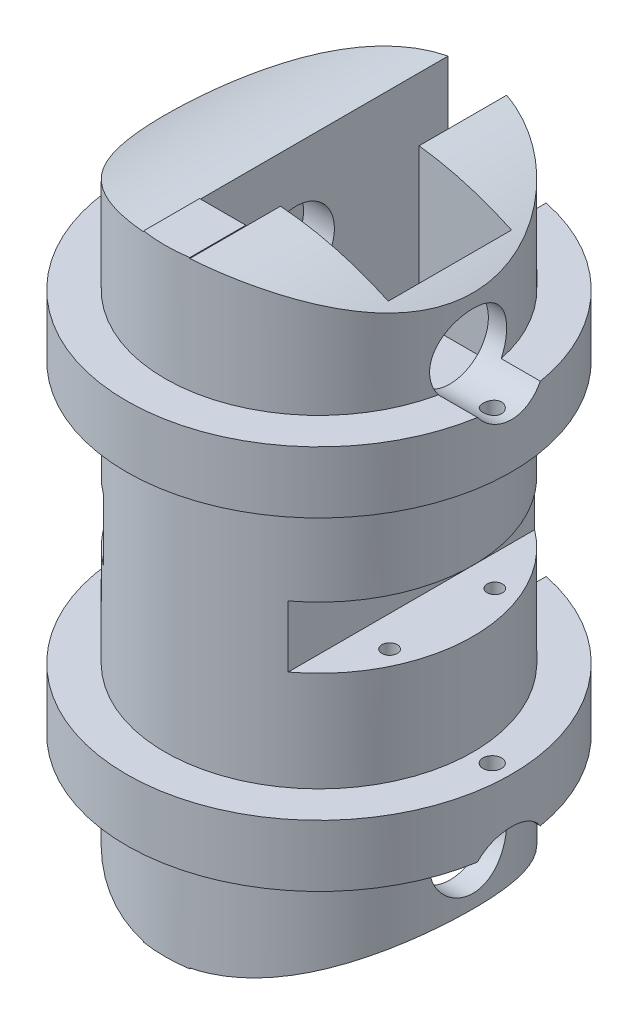
SolidWorks part; units mm, degrees
material "PET"
ref_plane "Front Plane" through (0, 0, 0) normal (0, 0, 1) x (1, 0, 0)
ref_plane "Top Plane" through (0, 0, 0) normal (0, 1, 0) x (1, 0, 0)
ref_plane "Right Plane" through (0, 0, 0) normal (1, 0, 0) x (0, 0, -1)
sketch "Sketch1" plane through (0, 0, 0) normal (0, 1, 0) x (1, 0, 0)
  circle A0 centre (0, 0) radius 10
  dimension "D1" = 20
extrude "Boss-Extrude1" add sketch "Sketch1" along normal mid plane 40
sketch "Sketch2" plane through (0, 0, 0) normal (0, 0, 1) x (1, 0, 0)
  circle A0 centre (0, 0) radius 20
  circle A1 centre (0, 0) radius 24.8561
extrude "Cut-Extrude3" cut sketch "Sketch2" against normal mid plane 40
ref_plane "Plane1" through (0, 20, 0) normal (0, 1, 0) x (1, 0, 0)
sketch "Sketch5" plane through (0, 20, 0) normal (0, 1, 0) x (1, 0, 0)
  line L1 (-1.5, 10) -> (1.5, 10)
  line L2 (-1.5, 10) -> (-1.5, -10)
  line L3 (-1.5, -10) -> (1.5, -10)
  line L4 (1.5, 10) -> (1.5, -10)
  point P4 (0, 10)
  point P6 (1.5, 0)
  dimension "D1" = 20
  dimension "D2" = 3
extrude "Cut-Extrude4" cut sketch "Sketch5" against normal blind 10
sketch "Sketch6" plane through (1.5, 0, 0) normal (-1, 0, 0) x (0, 0, 1)
  line L1 (9.8869, 19.9437) -> (-9.8869, 19.9437) construction
  circle A0 centre (0, 13.9437) radius 2.5
  circle A2 centre (0, 13.9437) radius 6
  dimension "D1" = 5
  dimension "D2" = 12
extrude "Cut-Extrude5" cut sketch "Sketch6" against normal blind 20 and the other way blind 5 contours A0
sketch "Sketch7" plane through (0, 20, 0) normal (0, 1, 0) x (1, 0, 0)
  line L0 (1.5, -9.8869) -> (1.5, 9.8869) construction
  line L1 (1.5, -4) -> (8.5, -4)
  line L2 (1.5, -4) -> (1.5, 4)
  line L3 (1.5, 4) -> (8.5, 4)
  line L4 (8.5, -4) -> (8.5, 4)
  point P4 (8.5, 0)
  point P8 (1.5, 0)
  dimension "D1" = 7
  dimension "D2" = 8
extrude "Cut-Extrude7" cut sketch "Sketch7" against normal up to surface (10 mm away) contours L1 L4 L3 L2 up to face at (0, 10, 0)
sketch "Sketch8" plane through (0, 10, 0) normal (0, 1, 0) x (1, 0, 0)
  line L0 (8.5, -4) -> (1.5, -4) construction
  line L1 (8.5, -4) -> (8.5, 4) construction
  circle A0 centre (8, -3.4149) radius 0.5
  dimension "D3" = 1
  dimension "D1" = 0.5851
  dimension "D2" = 0.5
extrude "Cut-Extrude8" cut sketch "Sketch8" against normal blind 30
sketch "Sketch9" plane through (0, 10, 0) normal (0, 1, 0) x (1, 0, 0)
  line L1 (0.5, 4) -> (2.5, 4)
  line L2 (0.5, 4) -> (0.5, 11.4751)
  line L3 (0.5, 11.4751) -> (2.5, 11.4751)
  line L4 (2.5, 4) -> (2.5, 11.4751)
  point P4 (1.5, 4)
  dimension "D1" = 2
extrude "Cut-Extrude9" cut sketch "Sketch9" along normal blind 23
mirror "Mirror2" about plane through (0, 0, 0) normal (0, 1, 0) of "Cut-Extrude9", "Cut-Extrude3", "Cut-Extrude5", "Cut-Extrude7", "Cut-Extrude8", "Cut-Extrude4"
mirror "Mirror3" about plane through (0, 0, 0) normal (0, 0, 1) of "Cut-Extrude8"
sketch "Sketch10" plane through (0, 10, 0) normal (0, 1, 0) x (1, 0, 0)
  line L0 (-1.5, 9.8869) -> (-1.5, -9.8869) construction
  line L1 (-1.5, -12.0623) -> (1.5, -12.0623)
  line L2 (-1.5, -12.0623) -> (-1.5, 12.1446)
  line L3 (-1.5, 12.1446) -> (1.5, 12.1446)
  line L4 (1.5, -12.0623) -> (1.5, 12.1446)
extrude "Cut-Extrude10" cut sketch "Sketch10" against normal blind 2.5
mirror "Mirror4" about plane through (0, 0, 0) normal (0, 1, 0) of "Cut-Extrude10"
sketch "Sketch11" plane through (0, -10, 0) normal (0, -1, 0) x (-1, 0, 0)
  line L1 (-0.5, -1.6113) -> (-2.5, -1.6113)
  line L2 (-0.5, -1.6113) -> (-0.5, -11.5424)
  line L3 (-0.5, -11.5424) -> (-2.5, -11.5424)
  line L4 (-2.5, -1.6113) -> (-2.5, -11.5424)
  line L5 (-1.5, -9.8869) -> (-1.5, 9.8869) construction
  point P4 (-1.5, -1.6113)
  dimension "D1" = 2
extrude "Cut-Extrude11" [suppressed] cut sketch "Sketch11" along normal blind 11.5
sketch "Sketch12" plane through (0, 0, 0) normal (0, 0, 1) x (1, 0, 0)
  line L0 (-10, 17.3205) -> (-10, -17.3205) construction
  line L1 (-10, -2) -> (10, -2)
  line L2 (-10, -2) -> (-10, 2)
  line L3 (-10, 2) -> (10, 2)
  line L4 (10, -2) -> (10, 2)
  line L5 (10, -11.4437) -> (10, 11.4437) construction
  line L7 (-6, 2) -> (6, 2)
  line L8 (-6, 2) -> (-6, -2)
  line L9 (-6, -2) -> (6, -2)
  line L10 (6, 2) -> (6, -2)
  point P8 (10, 0)
  dimension "D1" = 4
  dimension "D2" = 12
  dimension "D3" = 6
extrude "Cut-Extrude12" cut sketch "Sketch12" against normal mid plane 30 contours L8 L3 L2 L1 | L3 L10 L1 L4 region at (-8, 0, 0) region at (8, 0, 0)
sketch "Sketch13" plane through (0, 0, 0) normal (0, 0, 1) x (1, 0, 0)
  line L1 (-12, 6) -> (12, 6)
  line L2 (-12, 6) -> (-12, 10)
  line L3 (-12, 10) -> (12, 10)
  line L4 (12, 6) -> (12, 10)
  line L5 (-12, 10) -> (-7.9801, 10)
  line L6 (-12, 10) -> (-12, 6)
  line L7 (-12, 6) -> (-7.9801, 6)
  line L8 (-7.9801, 10) -> (-7.9801, 6)
  line L9 (12, 10) -> (8.9565, 10)
  line L10 (12, 10) -> (12, 6)
  line L11 (12, 6) -> (8.9565, 6)
  line L12 (8.9565, 10) -> (8.9565, 6)
  circle A0 centre (-10, 8) radius 1
  circle A1 centre (10, 8) radius 1
  point P4 (0, 6)
  point P11 (-12, 8)
  dimension "D6" = 2
  dimension "2" = 2
  dimension "D1" = 24
  dimension "D2" = 4
  dimension "D3" = 6
  dimension "D4" = 20
  dimension "D5" = 10
extrude "Boss-Extrude4" [suppressed] add sketch "Sketch13" along normal mid plane 2.5 contours L3 L12 L1 L4 A1 | L8 L3 L2 L1 A0
sketch "Sketch14" [suppressed] plane through (0, 0, 0) normal (0, 0, 1) x (1, 0, 0)
  line L0 (-10, 9) -> (-10, 7) construction
  circle A0 centre (10, 8) radius 1
  circle A1 centre (-10, 8) radius 1
ref_plane "Plane2" [suppressed] through (0, 8, 0) normal (0, 1, 0) x (1, 0, 0)
sketch "Sketch15" [suppressed] plane through (0, 8, 0) normal (0, 1, 0) x (1, 0, 0)
  arc A0 (-10, 0) -> (10, 0) centre (0, 0) ccw
sweep "Cut-Sweep1" [suppressed] cut path "Sketch15" circular profile diameter 2 parameters "D3"=2
sketch "Sketch29" [suppressed] plane through (0, 0, 0) normal (0, 0, 1) x (1, 0, 0)
  circle A0 centre (10, 8) radius 1
  circle A1 centre (-10, 8) radius 1
extrude "Cut-Extrude13" [suppressed] cut sketch "Sketch29" against normal blind 5
ref_plane "Plane3" [suppressed] through (0, 0, 0) normal (0, 0, 1) x (1, 0, 0)
sketch "Sketch36" [suppressed] plane through (0, 0, 0) normal (0, 0, 1) x (1, 0, 0)
  line L0 (10, 7) -> (10, 9) construction
  circle A0 centre (-10, 8) radius 1
  circle A1 centre (10, 8) radius 1
extrude "Cut-Extrude14" [suppressed] cut sketch "Sketch36" against normal up to surface and the other way up to surface
ref_plane "Plane4" through (0, 12.5, 0) normal (0, 1, 0) x (1, 0, 0)
sketch "Sketch37" plane through (0, 12.5, 0) normal (0, 1, 0) x (1, 0, 0)
  line L1 (-2.5, 16.1752) -> (2.5, 16.1752)
  line L2 (-2.5, 16.1752) -> (-2.5, 6.4344)
  line L3 (-2.5, 6.4344) -> (2.5, 6.4344)
  line L4 (2.5, 16.1752) -> (2.5, 6.4344)
  circle A0 centre (0, 0) radius 10
  circle A1 centre (0, 0) radius 12.5
  point P9 (0, 6.4344)
  dimension "D1" = 5
extrude "Boss-Extrude7" add sketch "Sketch37" against normal blind 4 contours L2 A1 L4 A0 region at (-2.8518, 12.5, -10.965)
mirror "Mirror5" about plane through (0, 0, 0) normal (0, 1, 0) of "Boss-Extrude7"
sketch "Sketch39" plane through (0, 0, 0) normal (1, 0, 0) x (0, 0, -1)
  circle A0 centre (0, 13.9437) radius 2.5
  circle A1 centre (0, -13.9437) radius 2.5
extrude "Cut-Extrude15" cut sketch "Sketch39" along normal blind 12.5
sketch "Sketch41" plane through (0, 7.5, 0) normal (0, 1, 0) x (1, 0, 0)
  line L0 (-1.5, -6.25) -> (1.5, -6.25)
  line L1 (-1.5, 9.8869) -> (-1.5, -9.8869) construction
  line L2 (1.5, -9.8869) -> (1.5, -4) construction
  circle A0 centre (0, 0) radius 12.5
  circle A1 centre (0, 0) radius 10
  line M2 (1.5, -9.8869) -> (1.5, 9.8869)
  line M4 (-1.5, 9.8869) -> (-1.5, -9.8869)
  arc M5 (-1.5, -9.8869) -> (1.5, -9.8869) centre (0, 0) ccw
  dimension "D1" = 6.25
extrude "Boss-Extrude8" add sketch "Sketch41" along normal blind 12.5 contours L0 M4 M5 M2 region at (0, 7.5, 8.1063)
mirror "Mirror6" about plane through (0, 0, 0) normal (0, 1, 0) of "Boss-Extrude8"
sketch "Sketch42" plane through (0, 12.5, 0) normal (0, 1, 0) x (1, 0, 0)
  circle A0 centre (11.25, 0) radius 0.6
  dimension "D1" = 1.2
  dimension "D2" = 11.25
extrude "Cut-Extrude16" cut sketch "Sketch42" against normal through all
mirror "Mirror7" about plane through (0, 0, 0) normal (1, 0, 0) of "Cut-Extrude16"
